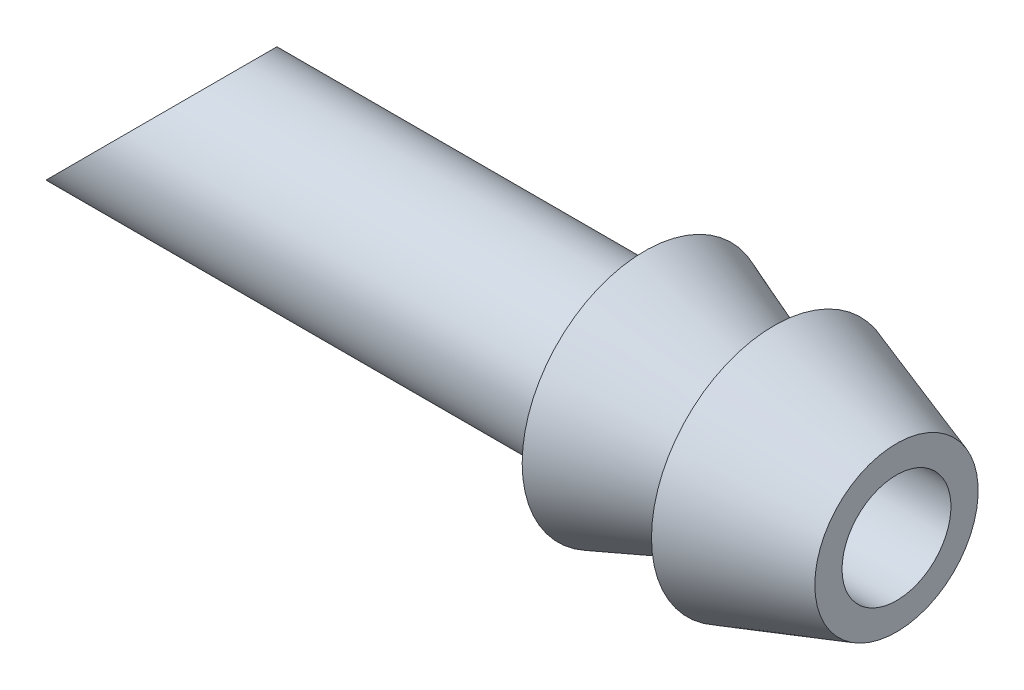
SolidWorks part; units mm, degrees
ref_plane "Front Plane" through (0, 0, 0) normal (0, 0, 1) x (1, 0, 0)
ref_plane "Top Plane" through (0, 0, 0) normal (0, 1, 0) x (1, 0, 0)
ref_plane "Right Plane" through (0, 0, 0) normal (1, 0, 0) x (0, 0, -1)
sketch "Sketch1" plane through (0, 0, 0) normal (0, 0, 1) x (1, 0, 0)
  line L0 (0, 0) -> (188.3019, 0) construction
  line L1 (22.1515, 3) -> (17.6515, 4.5)
  line L2 (-7.8485, 2) -> (22.1515, 2)
  line L3 (-7.8485, 2) -> (-7.8485, 3)
  line L4 (-7.8485, 3) -> (12.9015, 3)
  line L5 (22.1515, 2) -> (22.1515, 3)
  line L6 (17.6515, 4.5) -> (17.6515, 3)
  line L7 (16.9015, 3) -> (12.9015, 4.5)
  line L8 (12.9015, 4.5) -> (12.9015, 3)
  line L10 (16.9015, 3) -> (17.6515, 3)
  dimension "D1" = 3
  dimension "D2" = 1
  dimension "D3" = 30
  dimension "D4" = 4.5
  dimension "D5" = 4
  dimension "D6" = 1.5
  dimension "D7" = 1.5
  dimension "D8" = 0.75
revolve "Revolve1" add sketch "Sketch1" angle 360 about L0
sketch "Sketch2" plane through (0, 0, 0) normal (0, 0, 1) x (1, 0, 0)
  line L0 (-7.8485, -3) -> (-1.8485, 3)
  line L1 (12.9015, 3) -> (-7.8485, 3) construction
  line L2 (-1.8485, 3) -> (-7.8485, 3)
  line L3 (-7.8485, 3) -> (-7.8485, -3)
  dimension "D1" = 45
extrude "Cut-Extrude1" cut sketch "Sketch2" against normal blind 10 and the other way blind 10
